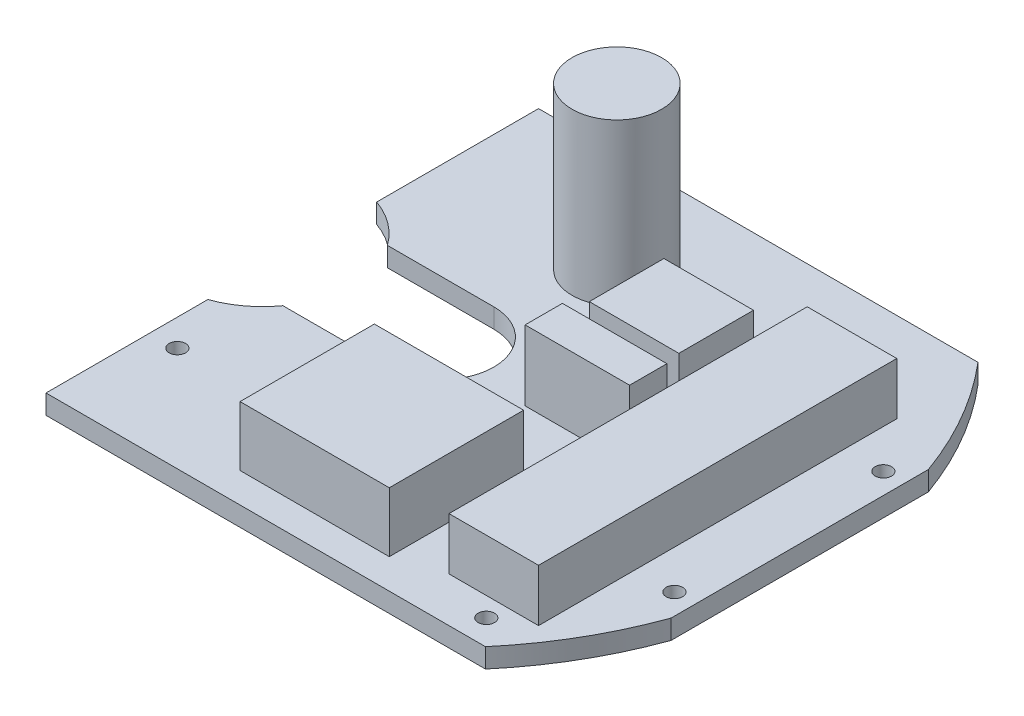
SolidWorks part; units mm, degrees
ref_plane "Front Plane" through (0, 0, 0) normal (0, 0, 1) x (1, 0, 0)
ref_plane "Top Plane" through (0, 0, 0) normal (0, 1, 0) x (1, 0, 0)
ref_plane "Right Plane" through (0, 0, 0) normal (1, 0, 0) x (0, 0, -1)
sketch "Sketch1" plane through (0, 0, 0) normal (0, 1, 0) x (1, 0, 0)
  line L0 (0, 23.0679) -> (0, -25.8926) construction
  line L1 (-38.5819, 0) -> (38.4586, 0) construction
  line L2 (49.3832, 41.91) -> (-25.4, 41.91)
  line L3 (0, 8.89) -> (-18.1016, 8.89)
  line L4 (0, -8.89) -> (-18.1016, -8.89)
  line L5 (-25.4, -14.3684) -> (-25.4, -41.91)
  line L6 (-25.4, 41.91) -> (-25.4, 14.3684)
  line L7 (-25.4, -41.91) -> (49.3832, -41.91)
  line L8 (60.96, 21.8868) -> (60.96, -21.8868)
  arc A0 (0, -8.89) -> (0, 8.89) centre (0, 0) ccw
  arc A1 (49.3832, -41.91) -> (60.96, -21.8868) centre (0, 0) ccw
  circle A2 centre (-30.48, 0) radius 12.7 construction
  arc A3 (-25.4, 14.3684) -> (-18.1016, 8.89) centre (-30.48, 0) cw
  arc A4 (-18.1016, -8.89) -> (-25.4, -14.3684) centre (-30.48, 0) cw
  arc A5 (60.96, 21.8868) -> (49.3832, 41.91) centre (0, 0) ccw
  dimension "D1" = 17.78
  dimension "D2" = 129.54
  dimension "D6" = 25.4
  dimension "D8" = 15.24
  dimension "D9" = 15.24
  dimension "D3" = 41.91
  dimension "D4" = 41.91
  dimension "D5" = 25.4
  dimension "D7" = 30.48
  dimension "D10" = 86.36
extrude "Boss-Extrude1" add sketch "Sketch1" along normal mid plane 3.302 contours A0 L3 A3 L6 L2 A5 L8 A1 L7 L5 A4 L4
sketch "Sketch2" plane through (0, 1.651, 0) normal (0, 1, 0) x (1, 0, 0)
  line L0 (-25.4, -41.91) -> (49.3832, -41.91) construction
  line L1 (-25.4, -14.3684) -> (-25.4, -41.91) construction
  circle A0 centre (-20.828, -24.13) radius 1.397
  circle A1 centre (13.462, -19.558) radius 1.397
  circle A2 centre (45.212, -37.592) radius 1.397
  circle A3 centre (57.404, -17.78) radius 1.397
  circle A4 centre (57.404, 17.78) radius 1.397
  circle A5 centre (-6.35, 29.21) radius 1.397
  dimension "D1" = 2.794
  dimension "D8" = 82.804
  dimension "D2" = 17.78
  dimension "D3" = 4.572
  dimension "D4" = 38.862
  dimension "D5" = 22.352
  dimension "D6" = 70.612
  dimension "D7" = 4.318
  dimension "D9" = 24.13
  dimension "D10" = 82.804
  dimension "D11" = 59.69
  dimension "D12" = 19.05
  dimension "D13" = 71.12
extrude "Cut-Extrude1" cut sketch "Sketch2" against normal through all both and the other way through all
sketch "Sketch3" plane through (0, 1.651, 0) normal (0, 1, 0) x (1, 0, 0)
  line L0 (-25.4, -41.91) -> (49.3832, -41.91) construction
  line L1 (-25.4, -14.3684) -> (-25.4, -41.91) construction
  circle A0 centre (4.986, 24.8498) radius 7.62
  point P4 (0, 0)
  dimension "D1" = 15.24
  dimension "D2" = 66.7598
  dimension "D3" = 30.386
extrude "Boss-Extrude2" add sketch "Sketch3" along normal blind 27.432
sketch "Sketch4" plane through (0, 1.651, 0) normal (0, 1, 0) x (1, 0, 0)
  line L0 (-25.4, -41.91) -> (49.3832, -41.91) construction
  line L1 (50.8, 26.67) -> (35.56, 26.67)
  line L2 (50.8, 26.67) -> (50.8, -34.29)
  line L3 (50.8, -34.29) -> (35.56, -34.29)
  line L4 (35.56, 26.67) -> (35.56, -34.29)
  line L5 (50.8, 26.67) -> (35.56, -34.29) construction
  line L6 (50.8, -34.29) -> (35.56, 26.67) construction
  line L7 (-25.4, -14.3684) -> (-25.4, -41.91) construction
  point P0 (43.18, -3.81)
  dimension "D1" = 15.24
  dimension "D2" = 60.96
  dimension "D3" = 7.62
  dimension "D4" = 60.96
extrude "Boss-Extrude3" add sketch "Sketch4" along normal blind 8.89
sketch "Sketch5" plane through (0, 1.651, 0) normal (0, 1, 0) x (1, 0, 0)
  line L0 (-25.4, -41.91) -> (49.3832, -41.91) construction
  line L1 (2.54, -13.97) -> (27.94, -13.97)
  line L2 (2.54, -13.97) -> (2.54, -36.83)
  line L3 (2.54, -36.83) -> (27.94, -36.83)
  line L4 (27.94, -13.97) -> (27.94, -36.83)
  line L5 (2.54, -13.97) -> (27.94, -36.83) construction
  line L6 (2.54, -36.83) -> (27.94, -13.97) construction
  line L7 (-25.4, -14.3684) -> (-25.4, -41.91) construction
  point P0 (15.24, -25.4)
  dimension "D1" = 25.4
  dimension "D2" = 22.86
  dimension "D3" = 5.08
  dimension "D4" = 27.94
extrude "Boss-Extrude4" add sketch "Sketch5" along normal blind 10.16
sketch "Sketch6" plane through (0, 1.651, 0) normal (0, 1, 0) x (1, 0, 0)
  line L0 (-25.4, -14.3684) -> (-25.4, -41.91) construction
  line L1 (17.272, 3.302) -> (35.052, 3.302)
  line L2 (17.272, 3.302) -> (17.272, -3.048)
  line L3 (17.272, -3.048) -> (35.052, -3.048)
  line L4 (35.052, 3.302) -> (35.052, -3.048)
  line L5 (17.272, 3.302) -> (35.052, -3.048) construction
  line L6 (17.272, -3.048) -> (35.052, 3.302) construction
  line L7 (-25.4, -41.91) -> (49.3832, -41.91) construction
  point P0 (26.162, 0.127)
  dimension "D1" = 17.78
  dimension "D2" = 6.35
  dimension "D3" = 42.672
  dimension "D4" = 38.862
extrude "Boss-Extrude5" add sketch "Sketch6" along normal blind 11.938
sketch "Sketch7" plane through (0, 1.651, 0) normal (0, 1, 0) x (1, 0, 0)
  line L0 (-25.4, -14.3684) -> (-25.4, -41.91) construction
  line L1 (31.496, 8.89) -> (16.256, 8.89)
  line L2 (31.496, 8.89) -> (31.496, 21.59)
  line L3 (31.496, 21.59) -> (16.256, 21.59)
  line L4 (16.256, 8.89) -> (16.256, 21.59)
  line L5 (31.496, 8.89) -> (16.256, 21.59) construction
  line L6 (31.496, 21.59) -> (16.256, 8.89) construction
  line L7 (-25.4, -41.91) -> (49.3832, -41.91) construction
  point P0 (23.876, 15.24)
  dimension "D1" = 15.24
  dimension "D2" = 12.7
  dimension "D3" = 41.656
  dimension "D4" = 50.8
extrude "Boss-Extrude6" add sketch "Sketch7" along normal blind 8.89
